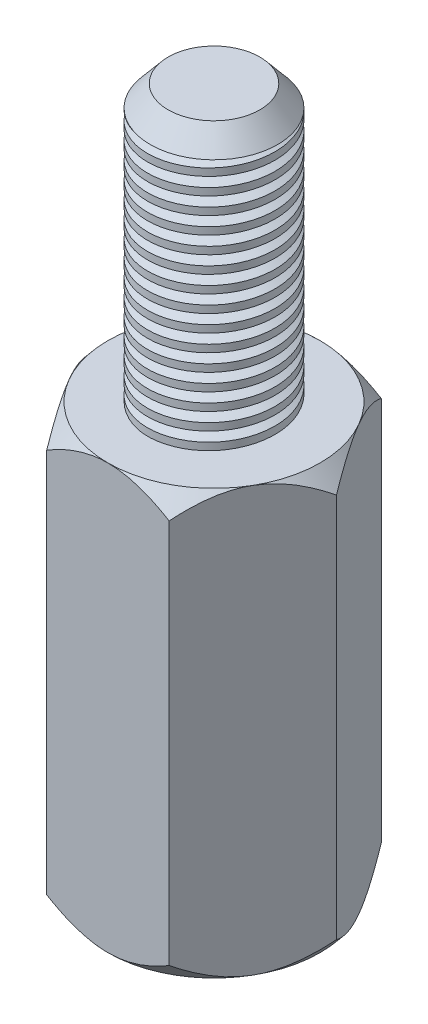
SolidWorks part; units mm, degrees
ref_plane "Front Plane" through (0, 0, 0) normal (0, 0, 1) x (1, 0, 0)
ref_plane "Top Plane" through (0, 0, 0) normal (0, 1, 0) x (1, 0, 0)
ref_plane "Right Plane" through (0, 0, 0) normal (1, 0, 0) x (0, 0, -1)
sketch "Sketch1" plane through (0, 0, 0) normal (0, 1, 0) x (1, 0, 0)
  line L1 (2.8868, 0) -> (1.4434, 2.5)
  line L2 (1.4434, 2.5) -> (-1.4434, 2.5)
  line L3 (-1.4434, 2.5) -> (-2.8868, 0)
  line L4 (-2.8868, 0) -> (-1.4434, -2.5)
  line L5 (-1.4434, -2.5) -> (1.4434, -2.5)
  line L6 (1.4434, -2.5) -> (2.8868, 0)
  circle A0 centre (0, 0) radius 2.5 construction
  dimension "D1" = 5
extrude "Boss-Extrude1" add sketch "Sketch1" along normal blind 10
sketch "Sketch2" plane through (0, 0, 0) normal (0, -1, 0) x (1, 0, 0)
  circle A0 centre (0, 0) radius 1.5
  dimension "D1" = 3
extrude "Cut-Extrude1" cut sketch "Sketch2" against normal blind 7
sketch "Sketch3" plane through (0, 10, 0) normal (0, 1, 0) x (1, 0, 0)
  circle A0 centre (0, 0) radius 2.5
  dimension "D1" = 5
extrude "Cut-Extrude2" cut sketch "Sketch3" against normal blind 0.5 draft 40 flip side to cut
sketch "Sketch4" plane through (0, 10, 0) normal (0, 1, 0) x (1, 0, 0)
  circle A0 centre (0, 0) radius 1.5
  dimension "D1" = 3
extrude "Boss-Extrude3" add sketch "Sketch4" along normal blind 6
sketch "Sketch5" plane through (0, 0, 0) normal (0, -1, 0) x (1, 0, 0)
  circle A0 centre (0, 0) radius 2.5
  dimension "D1" = 5
extrude "Cut-Extrude3" cut sketch "Sketch5" against normal blind 0.5 draft 40 flip side to cut
sketch "Sketch6" plane through (0, 16, 0) normal (0, 1, 0) x (1, 0, 0)
  circle A0 centre (0, 0) radius 1.5
  circle A1 centre (0, 0) radius 1.5 construction
  dimension "D1" = 3
curve "Helix/Spiral1" pitch 0.4 height 6 radius 1.5 centre (0, 16, 0) axis (0, -1, 0) start towards (1, 0, 0)
sketch "Sketch7" plane through (0, 0, 0) normal (0, 0, 1) x (1, 0, 0)
  line L1 (1.3037, 16) -> (1.5981, 15.83)
  line L2 (1.5981, 15.83) -> (1.5981, 16.17)
  line L3 (1.5981, 16.17) -> (1.3037, 16)
  circle A0 centre (1.5, 16) radius 0.0981 construction
  dimension "D1" = 0.1963
sweep "Cut-Sweep1" cut profiles "Sketch7" path "Helix/Spiral1" align with end faces yes
sketch "Sketch8" plane through (0, 16, 0) normal (0, 1, 0) x (1, 0, 0)
  circle A0 centre (0, 0) radius 1.5
  dimension "D1" = 3
extrude "Boss-Extrude4" add sketch "Sketch8" along normal blind 0.5 draft 40
sketch "Sketch9" plane through (0, 7, 0) normal (0, -1, 0) x (1, 0, 0)
  circle A0 centre (0, 0) radius 1.5
  circle A1 centre (0, 0) radius 1.5 construction
  dimension "D1" = 3
curve "Helix/Spiral3" pitch 0.4 height 7.5 radius 1.5 left hand yes centre (0, 7, 0) axis (0, -1, 0) start towards (1, 0, 0)
sketch "Sketch10" plane through (0, 0, 0) normal (1, 0, 0) x (0, 0, -1)
  line L1 (-1.6906, -0.4945) -> (-1.3962, -0.6645)
  line L2 (-1.3962, -0.6645) -> (-1.3962, -0.3245)
  line L3 (-1.3962, -0.3245) -> (-1.6906, -0.4945)
  circle A0 centre (-1.4943, -0.4945) radius 0.0981 construction
  spline S0 degree 3 poles (0, 7) (0.1951, 6.9917) (0.5895, 6.975) (1.0881, 6.95) (1.4219, 6.925) (1.539, 6.9) (1.4219, 6.875) (1.0883, 6.85) (0.589, 6.825) (0, 6.8) (-0.589, 6.775) (-1.0883, 6.75) (-1.4219, 6.725) (-1.5391, 6.7) (-1.4219, 6.675) (-1.0883, 6.65) (-0.589, 6.625) (0, 6.6) (0.589, 6.575) (1.0883, 6.55) (1.4219, 6.525) (1.5391, 6.5) (1.4219, 6.475) (1.0883, 6.45) (0.589, 6.425) (0, 6.4) (-0.589, 6.375) (-1.0883, 6.35) (-1.4219, 6.325) (-1.5391, 6.3) (-1.4219, 6.275) (-1.0883, 6.25) (-0.589, 6.225) (0, 6.2) (0.589, 6.175) (1.0883, 6.15) (1.4219, 6.125) (1.5391, 6.1) (1.4219, 6.075) (1.0883, 6.05) (0.589, 6.025) (0, 6) (-0.589, 5.975) (-1.0883, 5.95) (-1.4219, 5.925) (-1.5391, 5.9) (-1.4219, 5.875) (-1.0883, 5.85) (-0.589, 5.825) (0, 5.8) (0.589, 5.775) (1.0883, 5.75) (1.4219, 5.725) (1.5391, 5.7) (1.4219, 5.675) (1.0883, 5.65) (0.589, 5.625) (0, 5.6) (-0.589, 5.575) (-1.0883, 5.55) (-1.4219, 5.525) (-1.5391, 5.5) (-1.4219, 5.475) (-1.0883, 5.45) (-0.589, 5.425) (0, 5.4) (0.589, 5.375) (1.0883, 5.35) (1.4219, 5.325) (1.5391, 5.3) (1.4219, 5.275) (1.0883, 5.25) (0.589, 5.225) (0, 5.2) (-0.589, 5.175) (-1.0883, 5.15) (-1.4219, 5.125) (-1.5391, 5.1) (-1.4219, 5.075) (-1.0883, 5.05) (-0.589, 5.025) (0, 5) (0.589, 4.975) (1.0883, 4.95) (1.4219, 4.925) (1.5391, 4.9) (1.4219, 4.875) (1.0883, 4.85) (0.589, 4.825) (0, 4.8) (-0.589, 4.775) (-1.0883, 4.75) (-1.4219, 4.725) (-1.5391, 4.7) (-1.4219, 4.675) (-1.0883, 4.65) (-0.589, 4.625) (0, 4.6) (0.589, 4.575) (1.0883, 4.55) (1.4219, 4.525) (1.5391, 4.5) (1.4219, 4.475) (1.0883, 4.45) (0.589, 4.425) (0, 4.4) (-0.589, 4.375) (-1.0883, 4.35) (-1.4219, 4.325) (-1.5391, 4.3) (-1.4219, 4.275) (-1.0883, 4.25) (-0.589, 4.225) (0, 4.2) (0.589, 4.175) (1.0883, 4.15) (1.4219, 4.125) (1.5391, 4.1) (1.4219, 4.075) (1.0883, 4.05) (0.589, 4.025) (0, 4) (-0.589, 3.975) (-1.0883, 3.95) (-1.4219, 3.925) (-1.5391, 3.9) (-1.4219, 3.875) (-1.0883, 3.85) (-0.589, 3.825) (0, 3.8) (0.589, 3.775) (1.0883, 3.75) (1.4219, 3.725) (1.5391, 3.7) (1.4219, 3.675) (1.0883, 3.65) (0.589, 3.625) (0, 3.6) (-0.589, 3.575) (-1.0883, 3.55) (-1.4219, 3.525) (-1.5391, 3.5) (-1.4219, 3.475) (-1.0883, 3.45) (-0.589, 3.425) (0, 3.4) (0.589, 3.375) (1.0883, 3.35) (1.4219, 3.325) (1.5391, 3.3) (1.4219, 3.275) (1.0883, 3.25) (0.589, 3.225) (0, 3.2) (-0.589, 3.175) (-1.0883, 3.15) (-1.4219, 3.125) (-1.5391, 3.1) (-1.4219, 3.075) (-1.0883, 3.05) (-0.589, 3.025) (0, 3) (0.589, 2.975) (1.0883, 2.95) (1.4219, 2.925) (1.5391, 2.9) (1.4219, 2.875) (1.0883, 2.85) (0.589, 2.825) (0, 2.8) (-0.589, 2.775) (-1.0883, 2.75) (-1.4219, 2.725) (-1.5391, 2.7) (-1.4219, 2.675) (-1.0883, 2.65) (-0.589, 2.625) (0, 2.6) (0.589, 2.575) (1.0883, 2.55) (1.4219, 2.525) (1.5391, 2.5) (1.4219, 2.475) (1.0883, 2.45) (0.589, 2.425) (0, 2.4) (-0.589, 2.375) (-1.0883, 2.35) (-1.4219, 2.325) (-1.5391, 2.3) (-1.4219, 2.275) (-1.0883, 2.25) (-0.589, 2.225) (0, 2.2) (0.589, 2.175) (1.0883, 2.15) (1.4219, 2.125) (1.5391, 2.1) (1.4219, 2.075) (1.0883, 2.05) (0.589, 2.025) (0, 2) (-0.589, 1.975) (-1.0883, 1.95) (-1.4219, 1.925) (-1.5391, 1.9) (-1.4219, 1.875) (-1.0883, 1.85) (-0.589, 1.825) (0, 1.8) (0.589, 1.775) (1.0883, 1.75) (1.4219, 1.725) (1.5391, 1.7) (1.4219, 1.675) (1.0883, 1.65) (0.589, 1.625) (0, 1.6) (-0.589, 1.575) (-1.0883, 1.55) (-1.4219, 1.525) (-1.5391, 1.5) (-1.4219, 1.475) (-1.0883, 1.45) (-0.589, 1.425) (0, 1.4) (0.589, 1.375) (1.0883, 1.35) (1.4219, 1.325) (1.5391, 1.3) (1.4219, 1.275) (1.0883, 1.25) (0.589, 1.225) (0, 1.2) (-0.589, 1.175) (-1.0883, 1.15) (-1.4219, 1.125) (-1.5391, 1.1) (-1.4219, 1.075) (-1.0883, 1.05) (-0.589, 1.025) (0, 1) (0.589, 0.975) (1.0883, 0.95) (1.4219, 0.925) (1.5391, 0.9) (1.4219, 0.875) (1.0883, 0.85) (0.589, 0.825) (0, 0.8) (-0.589, 0.775) (-1.0883, 0.75) (-1.4219, 0.725) (-1.5391, 0.7) (-1.4219, 0.675) (-1.0883, 0.65) (-0.589, 0.625) (0, 0.6) (0.589, 0.575) (1.0883, 0.55) (1.4219, 0.525) (1.5391, 0.5) (1.4219, 0.475) (1.0883, 0.45) (0.589, 0.425) (0, 0.4) (-0.589, 0.375) (-1.0883, 0.35) (-1.4219, 0.325) (-1.5391, 0.3) (-1.4219, 0.275) (-1.0883, 0.25) (-0.589, 0.225) (0, 0.2) (0.589, 0.175) (1.0883, 0.15) (1.4219, 0.125) (1.5391, 0.1) (1.4219, 0.075) (1.0883, 0.05) (0.589, 0.025) (0, 0) (-0.589, -0.025) (-1.0883, -0.05) (-1.4219, -0.075) (-1.5391, -0.1) (-1.4219, -0.125) (-1.0883, -0.15) (-0.589, -0.175) (0, -0.2) (0.589, -0.225) (1.0883, -0.25) (1.4219, -0.275) (1.5391, -0.3) (1.4219, -0.325) (1.0883, -0.35) (0.589, -0.375) (0, -0.4) (-0.589, -0.425) (-1.0883, -0.45) (-1.4219, -0.475) (-1.5, -0.4917) (-1.5, -0.5) knots 0 0 0 0 0.003333 0.006667 0.01 0.013333 0.016667 0.02 0.023333 0.026667 0.03 0.033333 0.036667 0.04 0.043333 0.046667 0.05 0.053333 0.056667 0.06 0.063333 0.066667 0.07 0.073333 0.076667 0.08 0.083333 0.086667 0.09 0.093333 0.096667 0.1 0.103333 0.106667 0.11 0.113333 0.116667 0.12 0.123333 0.126667 0.13 0.133333 0.136667 0.14 0.143333 0.146667 0.15 0.153333 0.156667 0.16 0.163333 0.166667 0.17 0.173333 0.176667 0.18 0.183333 0.186667 0.19 0.193333 0.196667 0.2 0.203333 0.206667 0.21 0.213333 0.216667 0.22 0.223333 0.226667 0.23 0.233333 0.236667 0.24 0.243333 0.246667 0.25 0.253333 0.256667 0.26 0.263333 0.266667 0.27 0.273333 0.276667 0.28 0.283333 0.286667 0.29 0.293333 0.296667 0.3 0.303333 0.306667 0.31 0.313333 0.316667 0.32 0.323333 0.326667 0.33 0.333333 0.336667 0.34 0.343333 0.346667 0.35 0.353333 0.356667 0.36 0.363333 0.366667 0.37 0.373333 0.376667 0.38 0.383333 0.386667 0.39 0.393333 0.396667 0.4 0.403333 0.406667 0.41 0.413333 0.416667 0.42 0.423333 0.426667 0.43 0.433333 0.436667 0.44 0.443333 0.446667 0.45 0.453333 0.456667 0.46 0.463333 0.466667 0.47 0.473333 0.476667 0.48 0.483333 0.486667 0.49 0.493333 0.496667 0.5 0.503333 0.506667 0.51 0.513333 0.516667 0.52 0.523333 0.526667 0.53 0.533333 0.536667 0.54 0.543333 0.546667 0.55 0.553333 0.556667 0.56 0.563333 0.566667 0.57 0.573333 0.576667 0.58 0.583333 0.586667 0.59 0.593333 0.596667 0.6 0.603333 0.606667 0.61 0.613333 0.616667 0.62 0.623333 0.626667 0.63 0.633333 0.636667 0.64 0.643333 0.646667 0.65 0.653333 0.656667 0.66 0.663333 0.666667 0.67 0.673333 0.676667 0.68 0.683333 0.686667 0.69 0.693333 0.696667 0.7 0.703333 0.706667 0.71 0.713333 0.716667 0.72 0.723333 0.726667 0.73 0.733333 0.736667 0.74 0.743333 0.746667 0.75 0.753333 0.756667 0.76 0.763333 0.766667 0.77 0.773333 0.776667 0.78 0.783333 0.786667 0.79 0.793333 0.796667 0.8 0.803333 0.806667 0.81 0.813333 0.816667 0.82 0.823333 0.826667 0.83 0.833333 0.836667 0.84 0.843333 0.846667 0.85 0.853333 0.856667 0.86 0.863333 0.866667 0.87 0.873333 0.876667 0.88 0.883333 0.886667 0.89 0.893333 0.896667 0.9 0.903333 0.906667 0.91 0.913333 0.916667 0.92 0.923333 0.926667 0.93 0.933333 0.936667 0.94 0.943333 0.946667 0.95 0.953333 0.956667 0.96 0.963333 0.966667 0.97 0.973333 0.976667 0.98 0.983333 0.986667 0.99 0.993333 0.996667 1 1 1 1 construction
  dimension "D1" = 0.1963
  dimension "D2" = 1.3962
sweep "Cut-Sweep2" cut profiles "Sketch10" path "Helix/Spiral3" align with end faces yes
